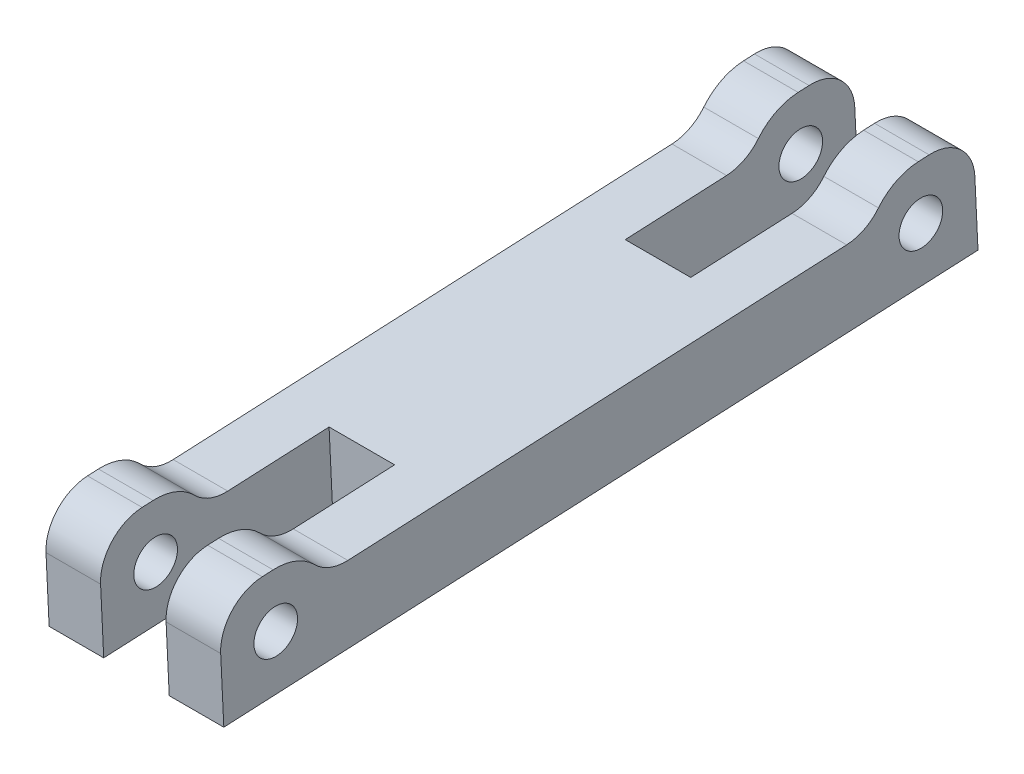
SolidWorks part; units mm, degrees
ref_plane "Front Plane" through (0, 0, 0) normal (0, 0, 1) x (1, 0, 0)
ref_plane "Top Plane" through (0, 0, 0) normal (0, 1, 0) x (1, 0, 0)
ref_plane "Right Plane" through (0, 0, 0) normal (1, 0, 0) x (0, 0, -1)
sketch "Sketch1" plane through (0, 0, 0) normal (1, 0, 0) x (0, 0, -1)
  line L0 (0, 0) -> (0, 10) construction
  line L1 (0, 0) -> (28.13, 0) construction
  line L2 (28.13, 0) -> (28.13, 12) construction
  line L3 (28.13, 0) -> (36.6153, 8.4853) construction
  line L4 (0, 0) -> (7.0711, 7.0711) construction
  line L5 (7.0711, 7.0711) -> (36.6153, 8.4853) construction
  line L6 (4.4544, 9.4487) -> (38.9929, 11.102)
  line L7 (38.9929, 11.102) -> (39.232, 6.1077)
  line L8 (39.232, 6.1077) -> (4.6935, 4.4544)
  line L9 (4.6935, 4.4544) -> (4.4544, 9.4487)
  line L10 (28.5049, 10.5999) -> (28.744, 5.6056)
  line L11 (14.9424, 9.9507) -> (15.1815, 4.9564)
  line L12 (21.7236, 10.2753) -> (21.9627, 5.281)
  circle A0 centre (28.13, 0) radius 12 construction
  circle A1 centre (36.6153, 8.4853) radius 1
  circle A2 centre (0, 0) radius 10 construction
  circle A3 centre (7.0711, 7.0711) radius 1
  dimension "D4" = 2
  dimension "D6" = 2
  dimension "D1" = 10
  dimension "D2" = 12
  dimension "D3" = 45
  dimension "D5" = 45
  dimension "D7" = 28.13
  dimension "D8" = 5
  dimension "D9" = 2.5
  dimension "D10" = 2.5
  dimension "D11" = 2.5
  dimension "D12" = 8
  dimension "D13" = 8
extrude "Boss-Extrude1" add sketch "Sketch1" along normal blind 1.5 and the other way blind 1.5 contours L12 L6 L11 L8 | L6 L12 L8 L10 region at (0, 7.6159, -18.4525) region at (0, 7.9405, -25.2338)
extrude "Boss-Extrude2" add sketch "Sketch1<3>" along normal blind 2.5 from offset 1.5 contours L11 L6 L9 L8 A3 | L12 L6 L11 L8 | L6 L12 L8 L10 | L6 L10 L8 L7 A1 region at (0, 7.2109, -9.9928) region at (0, 7.6159, -18.4525) region at (0, 7.9405, -25.2338) region at (0, 8.3454, -33.6936)
sketch "Sketch1<3>" plane through (0, 0, 0) normal (1, 0, 0) x (0, 0, -1) same geometry as "Sketch1"
extrude "Boss-Extrude3" add sketch "Sketch1<4>" against normal blind 2.5 from offset 1.5 contours L11 L6 L9 L8 A3 | L12 L6 L11 L8 | L6 L12 L8 L10 | L6 L10 L8 L7 A1 region at (0, 7.2109, -9.9928) region at (0, 7.6159, -18.4525) region at (0, 7.9405, -25.2338) region at (0, 8.3454, -33.6936) offset against normal yes
sketch "Sketch1<4>" plane through (0, 0, 0) normal (1, 0, 0) x (0, 0, -1) same geometry as "Sketch1"
fillet "Fillet1" radius 2 4 edges at (2.75, 11.102, -38.9929) (-2.75, 11.102, -38.9929) (2.75, 9.4487, -4.4544) (-2.75, 9.4487, -4.4544)
sketch "Sketch3" plane through (0, 0, 0) normal (1, 0, 0) x (0, 0, -1)
  line L0 (7.0711, 7.0711) -> (6.6207, 16.4799) construction
  line L1 (36.6153, 8.4853) -> (36.1468, 18.2721) construction
  line L2 (39.0885, 9.1042) -> (39.232, 6.1077) construction
  line L3 (4.6935, 4.4544) -> (4.55, 7.451) construction
  line L4 (9.3119, 8.1795) -> (34.2788, 9.3746)
  line L5 (7.0711, 7.0711) -> (6.8061, 12.606)
  line L6 (6.8061, 12.606) -> (36.3503, 14.0203)
  line L7 (36.3503, 14.0203) -> (36.6153, 8.4853)
  circle A0 centre (7.0711, 7.0711) radius 2.5
  circle A1 centre (36.6153, 8.4853) radius 2.5
  dimension "D1" = 5
  dimension "D2" = 5
  dimension "D3" = 1
extrude "Cut-Extrude1" cut sketch "Sketch3" against normal through all both and the other way through all contours A1 L7 L6 L5 A0 L4 region at (0, 11.1083, -21.6838)
fillet "Fillet2" radius 2 4 edges at (2.75, 9.3746, -34.2788) (-2.75, 9.3746, -34.2788) (2.75, 8.1795, -9.3119) (-2.75, 8.1795, -9.3119)
